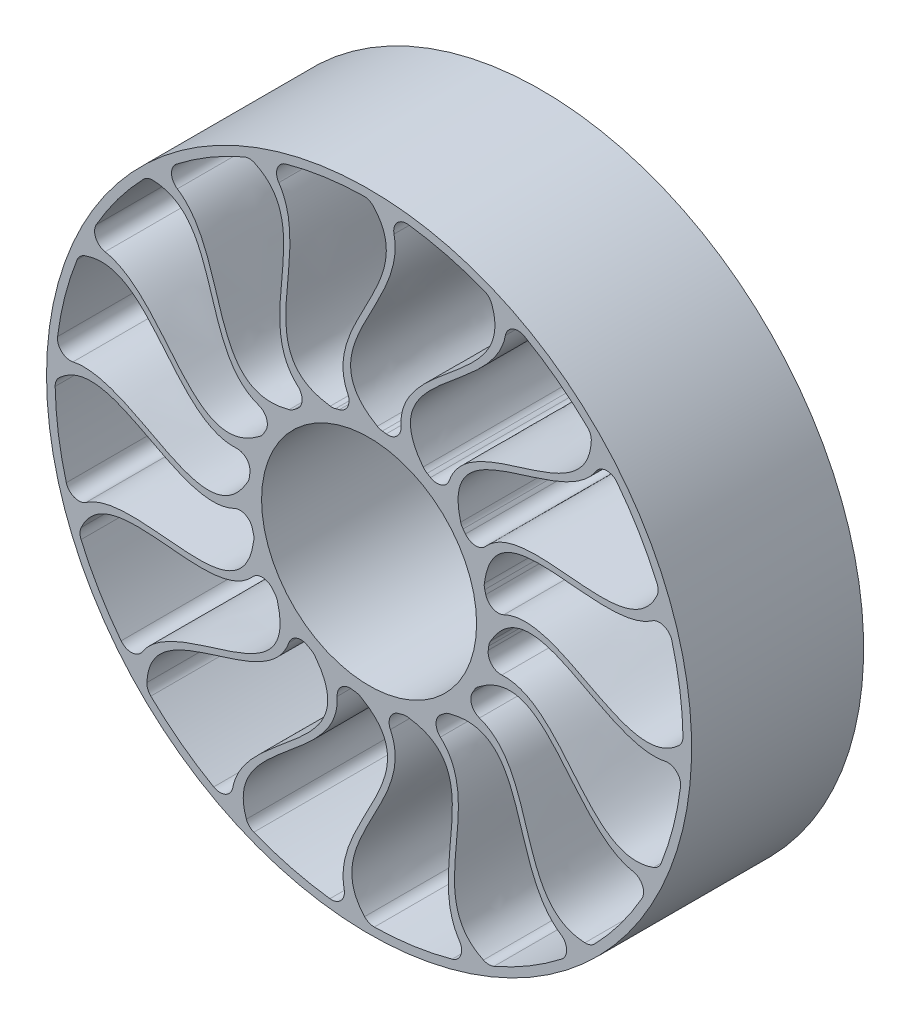
SolidWorks part; units mm, degrees
ref_plane "Front Plane" through (0, 0, 0) normal (0, 0, 1) x (1, 0, 0)
ref_plane "Top Plane" through (0, 0, 0) normal (0, 1, 0) x (1, 0, 0)
ref_plane "Right Plane" through (0, 0, 0) normal (1, 0, 0) x (0, 0, -1)
sketch "Sketch1" plane through (0, 0, 0) normal (0, 0, 1) x (1, 0, 0)
  circle A0 centre (0, 0) radius 25
  circle A1 centre (0, 0) radius 28
  dimension "D1" = 50
  dimension "D2" = 3
extrude "Boss-Extrude1" add sketch "Sketch1" along normal blind 40
sketch "Sketch2" plane through (0, 0, 40) normal (0, 0, 1) x (1, 0, 0)
  line L0 (0, 0) -> (0, 75) construction
  line L1 (0, 0) -> (0, -28) construction
  line L2 (-1.5252, 49.6735) -> (0.0715, 52.7362) construction
  line L3 (-0.2816, 49.1505) -> (1.4519, 52.4642) construction
  circle A0 centre (0, 0) radius 28 construction
  circle A1 centre (0, 0) radius 75 construction
  arc A2 (-2.5, 74.9583) -> (2.5, 74.9583) centre (0, 0) cw
  arc A3 (-2.5, 27.8882) -> (2.5, 27.8882) centre (0, 0) cw
  spline S0 degree 3 poles (-2.5, 27.8882) (-16.7498, 42.693) (17.6408, 61.7864) (-2.5, 74.9583) knots 0 0 0 0 1 1 1 1
  spline S1 degree 3 poles (2.5, 27.8882) (-18.3655, 39.0948) (16.8702, 59.4629) (2.5, 74.9583) knots 0 0 0 0 1 1 1 1
  point P5 (0, 28)
  dimension "D1" = 150
  dimension "D2" = 2
  dimension "D3" = 2
  dimension "D4" = 5
  dimension "D5" = 5
  dimension "D6" = 4
  dimension "D7" = 4
  dimension "D8" = 10
  dimension "D9" = 7
extrude "Support" add sketch "Sketch2" against normal through all
sketch "Sketch3" plane through (0, 0, 40) normal (0, 0, 1) x (1, 0, 0)
  circle A0 centre (0, 0) radius 75
  circle A1 centre (0, 0) radius 73
  dimension "D1" = 2
extrude "WheelRim" add sketch "Sketch3" against normal through all
fillet "SupportFillet" radius 3 4 edges at (2.5, 27.8882, 20) (-2.5, 27.8882, 20) (0.0588, 73, 20) (4.1191, 72.8837, 20)
pattern_circular "CirPattern1" count 16 over 360 about axis through (0, 0, 40) along (0, 0, -1) of "SupportFillet", "Support"
sketch "Sketch4" plane through (0, 0, 40) normal (0, 0, 1) x (1, 0, 0)
  circle A0 centre (0, 0) radius 27.1897
  circle A1 centre (0, 0) radius 129.6117
extrude "Bore only" [suppressed] cut sketch "Sketch4" against normal through all
